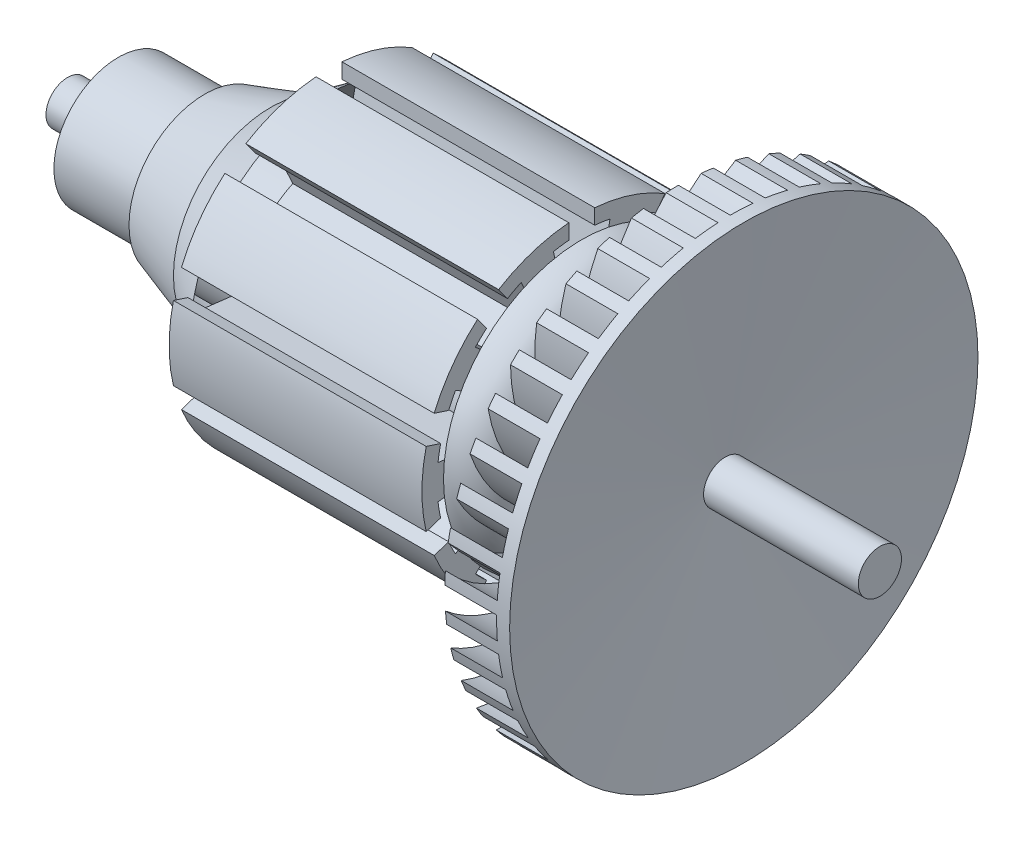
SolidWorks part; units mm, degrees
ref_plane "Front Plane" through (0, 0, 0) normal (0, 0, 1) x (1, 0, 0)
ref_plane "Top Plane" through (0, 0, 0) normal (0, 1, 0) x (1, 0, 0)
ref_plane "Right Plane" through (0, 0, 0) normal (1, 0, 0) x (0, 0, -1)
sketch "Sketch1" plane through (0, 0, 0) normal (1, 0, 0) x (0, 0, -1)
  circle A0 centre (0, 0) radius 18.5
  dimension "D1" = 37
extrude "Boss-Extrude1" add sketch "Sketch1" along normal mid plane 29.25
sketch "Sketch2" plane through (14.625, 0, 0) normal (1, 0, 0) x (0, 0, -1)
  line L0 (-3.2678, 16.4282) -> (-1.9509, 9.8079)
  line L1 (-1.5, 20.3173) -> (1.5, 20.3173)
  line L2 (-1.5, 20.3173) -> (-1.5, 16.6827)
  line L3 (3.2678, 16.4282) -> (1.9509, 9.8079)
  line L4 (1.5, 20.3173) -> (1.5, 16.6827)
  line L5 (-1.5, 20.3173) -> (1.5, 16.6827) construction
  line L6 (-1.5, 16.6827) -> (1.5, 20.3173) construction
  line L7 (0, 20.3173) -> (0, 0) construction
  circle A0 centre (0, 0) radius 18.5 construction
  arc A1 (-3.2678, 16.4282) -> (-1.5, 16.6827) centre (0, 0) cw
  arc A2 (1.5, 16.6827) -> (3.2678, 16.4282) centre (0, 0) cw
  arc A3 (-1.9509, 9.8079) -> (1.9509, 9.8079) centre (0, 0) cw
  point P0 (0, 18.5)
  dimension "D1" = 1.75
  dimension "D4" = 10
  dimension "D2" = 3
  dimension "D3" = 22.5
extrude "Cut-Extrude1" cut sketch "Sketch2" against normal through all
pattern_circular "CirPattern1" count 10 over 360 about axis through (14.625, 0, 0) along (-1, 0, 0) of "Cut-Extrude1"
sketch "Sketch3" plane through (-14.625, 0, 0) normal (-1, 0, 0) x (0, 0, 1)
  circle A0 centre (0, 0) radius 2.5
  dimension "D1" = 5
extrude "Boss-Extrude2" add sketch "Sketch3" along normal offset from surface (30.25 mm away) 59.5 up to face at (14.625, 0, 0)
sketch "Sketch9" plane through (-44.875, 0, 0) normal (-1, 0, 0) x (0, 0, 1)
  circle A0 centre (0, 0) radius 2.5
  circle A1 centre (0, 0) radius 2.5 construction
extrude "Boss-Extrude7" add sketch "Sketch9" against normal blind 94
sketch "Sketch4" plane through (-44.875, 0, 0) normal (-1, 0, 0) x (0, 0, 1)
  circle A0 centre (0, 0) radius 4
  circle A1 centre (0, 0) radius 2.5 construction
  dimension "D1" = 8
extrude "Boss-Extrude3" add sketch "Sketch4" against normal up to next from offset 4 offset against normal yes
sketch "Sketch5" plane through (-40.875, 0, 0) normal (-1, 0, 0) x (0, 0, 1)
  circle A0 centre (0, 0) radius 7.44
  dimension "D1" = 14.88
extrude "Boss-Extrude4" add sketch "Sketch5" against normal up to next from offset 1.86 offset against normal yes
sketch "Sketch7" plane through (-39.015, 0, 0) normal (-1, 0, 0) x (0, 0, 1)
  circle A0 centre (0, 0) radius 8.435
  circle A1 centre (0, 0) radius 7.44 construction
  dimension "D1" = 16.87
extrude "Boss-Extrude5" add sketch "Sketch7" against normal up to next from offset 10.5 offset against normal yes
sketch "Sketch6" plane through (0, 0, 0) normal (0, 0, 1) x (1, 0, 0)
  line L0 (-29.015, 7.44) -> (-29.015, 8.75)
  line L1 (-29.015, 8.75) -> (-21.375, 11.25)
  line L2 (-21.375, 11.25) -> (-14.625, 16)
  line L3 (-14.625, 16) -> (-14.625, -1.7263) construction
  line L5 (-28.515, 0) -> (-39.015, 0) construction
  line L6 (-14.625, 16.4282) -> (-14.625, 9.8079) construction
  line L7 (-39.015, 7.44) -> (-39.015, -7.44) construction
  line L9 (-28.515, 7.44) -> (-39.015, 7.44) construction
  line L10 (-14.625, 16) -> (14.625, 16) construction
  line L11 (19.625, 11) -> (19.625, 4.25)
  line L12 (-50.4469, 0) -> (36.3005, 0) construction
  line L13 (-14.625, 0) -> (14.625, 0) construction
  line L14 (14.625, 7.1246) -> (14.625, 14.0359) construction
  arc A0 (14.625, 16) -> (19.625, 11) centre (14.625, 11) cw
  dimension "D8" = 5
  dimension "D1" = 10
  dimension "D2" = 11.25
  dimension "D3" = 16
  dimension "D4" = 8.75
  dimension "D5" = 6.75
  dimension "D6" = 8.5
  dimension "D7" = 5
surface "Clearance surface 1" sketch "Sketch6" parameters "D1"=360
sketch "Sketch8" plane through (14.625, 0, 0) normal (1, 0, 0) x (0, 0, -1)
  circle A0 centre (0, 0) radius 4.25
  dimension "D1" = 8.5
extrude "Boss-Extrude6" add sketch "Sketch8" along normal blind 8
sketch "Sketch10" plane through (14.625, 0, 0) normal (1, 0, 0) x (0, 0, -1)
  circle A0 centre (0, 0) radius 9
  circle A1 centre (0, 0) radius 2.5 construction
  dimension "D1" = 18
extrude "Boss-Extrude8" add sketch "Sketch10" along normal offset from surface (10.25 mm away) 48 from offset 8.5 up to face at (-14.625, 0, -8.435)
sketch "Sketch11" plane through (33.375, 0, 0) normal (1, 0, 0) x (0, 0, -1)
  circle A0 centre (0, 0) radius 27.1
  dimension "D1" = 54.2
extrude "Boss-Extrude9" add sketch "Sketch11" against normal blind 1.5
sketch "Sketch12" plane through (0, 0, 0) normal (0, 0, 1) x (1, 0, 0)
  line L0 (30.9866, -16.9455) -> (31.875, -27.1)
  line L5 (31.875, 27.1) -> (31.875, -27.1) construction
  line L6 (23.125, -9) -> (31.875, -9)
  line L7 (31.875, -9) -> (31.875, -27.1)
  arc A0 (23.125, -9) -> (30.9866, -16.9455) centre (22.2699, -17.7081) cw
  dimension "D1" = 5
  dimension "D2" = 8.75
revolve "Revolve1" add sketch "Sketch12" angle 360 about axis through (106.8308, 0, 0) along (-1, 0, 0)
sketch "Sketch13" plane through (33.375, 0, 0) normal (1, 0, 0) x (0, 0, -1)
  line L0 (0, 0) -> (6.5561, 26.295) construction
  line L1 (7.9233, 25.9159) -> (0, 0) construction
  line L2 (0, 0) -> (-0.9159, 17.476) construction
  line L3 (0, 17.5) -> (0, 0) construction
  arc A0 (7.9233, 25.9159) -> (0, 17.5) centre (16.3734, 10.0226) ccw
  arc A1 (6.5561, 26.295) -> (-0.9159, 17.476) centre (18.6202, 8.4988) ccw
  arc A2 (7.9233, 25.9159) -> (6.5561, 26.295) centre (0, 0) ccw
  arc A3 (0, 17.5) -> (-0.9159, 17.476) centre (0, 0) ccw
  circle A4 centre (0, 0) radius 27.1 construction
  circle A5 centre (0, 0) radius 27.1 construction
  dimension "D1" = 17.5
  dimension "D5" = 18
  dimension "D6" = 21.5
  dimension "D2" = 3
  dimension "D3" = 3
  dimension "D4" = 17
extrude "Boss-Extrude10" add sketch "Sketch13" against normal blind 10
pattern_circular "CirPattern2" count 42 over 360 about axis through (-14.625, 0, 0) along (1, 0, 0) of "Boss-Extrude10"
sketch "Sketch14" plane through (0, 0, 0) normal (0, 0, 1) x (1, 0, 0)
  line L0 (62.2208, 0) -> (-6.9081, 0) construction
  line L1 (17.3419, 0) -> (46.4836, 0) construction
  line L2 (25.875, -27.1) -> (24.6502, -13.1)
  line L3 (23.125, 4.3326) -> (23.125, -13.1) construction
  line L4 (23.125, -27.1) -> (25.875, -27.1)
  line L5 (33.375, -27.1) -> (31.2228, -2.5)
  line L6 (31.2228, -2.5) -> (33.375, -2.5)
  line L7 (33.375, -2.5) -> (33.375, -27.1)
  line L8 (33.375, -27.1) -> (33.375, 27.1) construction
  line L9 (30.9866, -16.9455) -> (31.875, -27.1) construction
  line L10 (23.125, 9) -> (23.125, -9) construction
  line L11 (31.875, -9) -> (31.875, -27.1) construction
  line L12 (24.6502, -13.1) -> (23.125, 4.3326) construction
  line L13 (23.125, -13.1) -> (23.125, -27.1)
  line L14 (23.125, -13.1) -> (24.6502, -13.1)
  line L15 (33.375, -2.5) -> (49.125, -2.5) construction
  dimension "D1" = 6
  dimension "D2" = 14
revolve "Cut-Revolve2" cut sketch "Sketch14" angle 360 about L0
ref_plane "Midwinding plane" through (0, 0, 0) normal (1, 0, 0) x (0, 0, -1)
